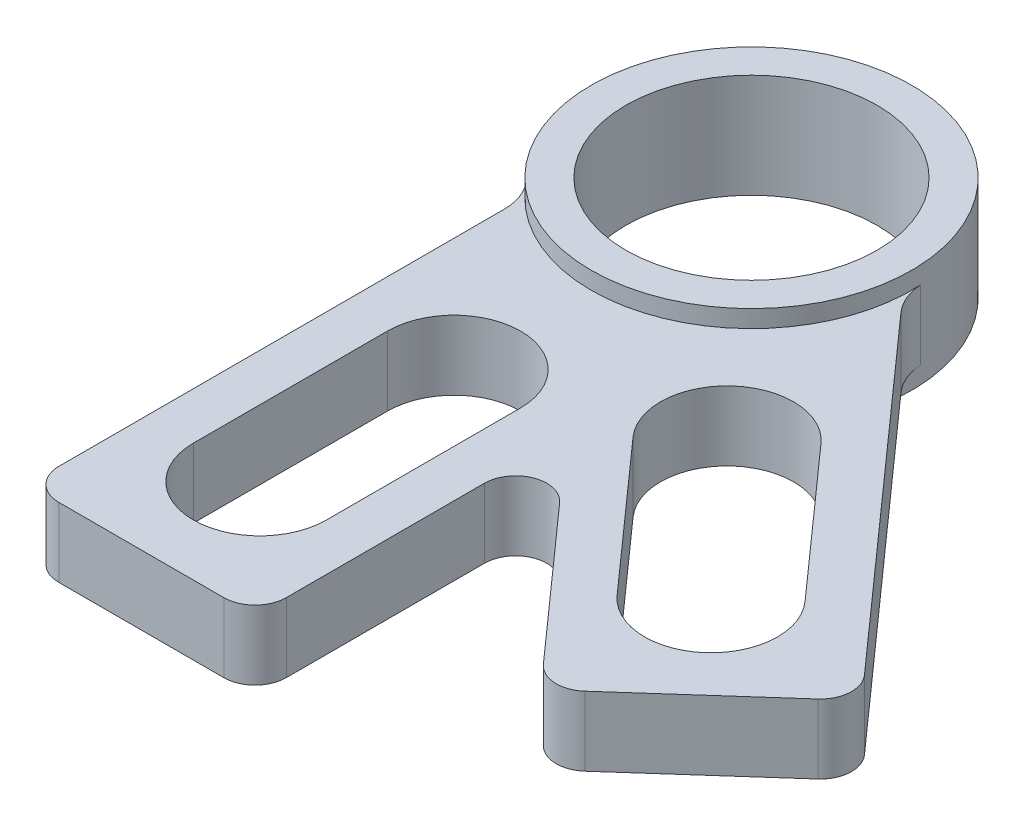
SolidWorks part; units mm, degrees
material "AISI 4130 Steel, annealed at 865C"
ref_plane "Front Plane" through (0, 0, 0) normal (0, 0, 1) x (1, 0, 0)
ref_plane "Top Plane" through (0, 0, 0) normal (0, 1, 0) x (1, 0, 0)
ref_plane "Right Plane" through (0, 0, 0) normal (1, 0, 0) x (0, 0, -1)
sketch "Sketch1" plane through (0, 0, 0) normal (0, 1, 0) x (1, 0, 0)
  line L0 (0, 0) -> (0, -55.88) construction
  line L1 (0, 0) -> (37.1508, -41.7419) construction
  line L2 (0, -45.0215) -> (0, -27.2415) construction
  line L3 (-6.096, -45.0215) -> (-6.096, -27.2415)
  line L4 (6.096, -45.0215) -> (6.096, -27.2415)
  line L5 (29.9318, -33.6307) -> (18.111, -20.3492) construction
  line L6 (25.3781, -37.6835) -> (13.5574, -24.402)
  line L7 (34.4854, -29.5779) -> (22.6647, -16.2964)
  line L8 (0, -55.88) -> (0, -51.1175) construction
  line L9 (37.1508, -41.7419) -> (33.9846, -38.1844) construction
  line L10 (-10.414, -55.88) -> (10.414, -55.88)
  line L11 (29.3717, -48.6655) -> (44.93, -34.8184)
  line L12 (-10.414, -55.88) -> (-10.414, -10.3482)
  line L13 (10.414, -55.88) -> (10.414, -27.3651)
  line L14 (44.93, -34.8184) -> (14.659, -0.8065)
  line L15 (29.3717, -48.6655) -> (10.414, -27.3651)
  line L16 (200.6019, -225.3923) -> (16.6401, -18.6965) construction
  line L22 (0, 0) -> (10.414, -27.3651) construction
  circle A0 centre (0, 0) radius 11.5062
  circle A1 centre (0, 0) radius 14.6812
  arc A2 (-6.096, -45.0215) -> (6.096, -45.0215) centre (0, -45.0215) ccw
  arc A3 (6.096, -27.2415) -> (-6.096, -27.2415) centre (0, -27.2415) ccw
  arc A4 (25.3781, -37.6835) -> (34.4854, -29.5779) centre (29.9318, -33.6307) ccw
  arc A5 (22.6647, -16.2964) -> (13.5574, -24.402) centre (18.111, -20.3492) ccw
  point P8 (0, -36.1315)
  point P13 (24.0214, -26.99)
  point P25 (0, -55.88)
  point P27 (37.1508, -41.7419)
  dimension "D2" = 29.3624
  dimension "D3" = 4.7625
  dimension "D4" = 4.318
  dimension "D5" = 17.78
  dimension "D6" = 55.88
  dimension "D7" = 20.828
extrude "Bearing_Insert_Extrude" add sketch "Sketch1" along normal mid plane 9.525 contours A1 A0 region at (-5.4385, 0, -13.1886)
extrude "Apex_Slot_Insert_Extrude" add sketch "Sketch1<4>" along normal mid plane 6.35 contours A1 L12 L10 L13 L15 L11 L14 A5 L7 A4 L6 A3 L4 A2 L3 region at (-9.6332, 0, 33.1141)
sketch "Sketch1<4>" plane through (0, 0, 0) normal (0, 1, 0) x (1, 0, 0) same geometry as "Sketch1"
fillet "Fillet1" radius 5.08 2 edges at (14.659, 0, 0.8065) (-10.414, 0, 10.3482)
fillet "Fillet2" radius 2.8575 5 edges at (44.93, 0, 34.8184) (29.3717, 0, 48.6655) (10.414, 0, 27.3651) (10.414, 0, 55.88) (-10.414, 0, 55.88)
equation "\"Apex_thickness\"= .25"
equation "\"Bearing_diameter\"= 0.906in"
equation "\"A-arm_angle\"= 39.1893"
equation "\"D1@Sketch1\"=\"Bearing_diameter\""
equation "\"D1@Apex_Slot_Insert_Extrude\"=\"Apex_thickness\""
